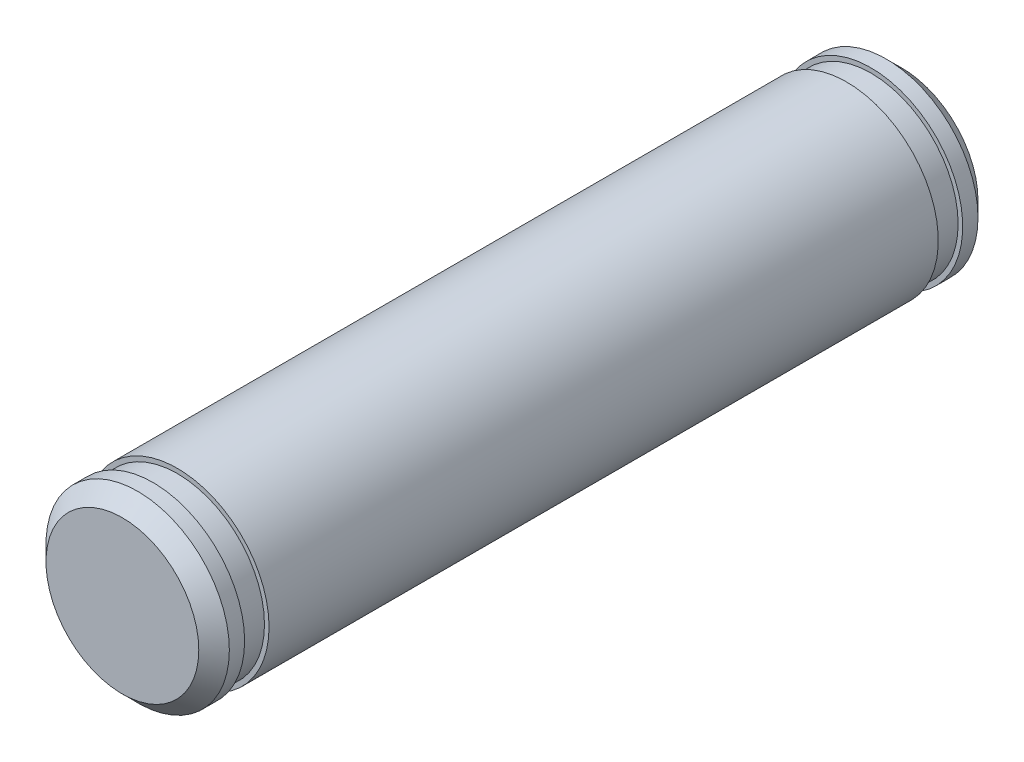
SolidWorks part; units mm, degrees
material "Stop 1060"
ref_plane "Płaszczyzna przednia" through (0, 0, 0) normal (0, 0, 1) x (1, 0, 0)
ref_plane "Płaszczyzna górna" through (0, 0, 0) normal (0, 1, 0) x (1, 0, 0)
ref_plane "Płaszczyzna prawa" through (0, 0, 0) normal (1, 0, 0) x (0, 0, -1)
sketch "Szkic1" plane through (0, 0, 0) normal (0, 0, 1) x (1, 0, 0)
  circle A0 centre (0, 0) radius 3
  dimension "D1" = 6
extrude "Dodanie-wyciągnięcie1" add sketch "Szkic1" along normal blind 25.5
chamfer "Sfazowanie1" distance 0.5 angle 45 2 edges at (3, 0, 0) (3, 0, 25.5)
sketch "Szkic2" plane through (0, 0, 25.5) normal (0, 0, 1) x (1, 0, 0)
  circle A0 centre (0, 0) radius 3
  circle A1 centre (0, 0) radius 2.85
  dimension "D1" = 6
  dimension "D2" = 5.7
extrude "Wytnij-wyciągnięcie1" cut sketch "Szkic2" against normal blind 0.8 from offset 1 offset against normal yes
sketch "Szkic3" plane through (0, 0, 0) normal (0, 0, -1) x (-1, 0, 0)
  circle A0 centre (0, 0) radius 2.85
  circle A1 centre (0, 0) radius 3
  dimension "D1" = 6
  dimension "D2" = 5.7
extrude "Wytnij-wyciągnięcie2" cut sketch "Szkic3" against normal blind 0.8 from offset 1 offset against normal yes
